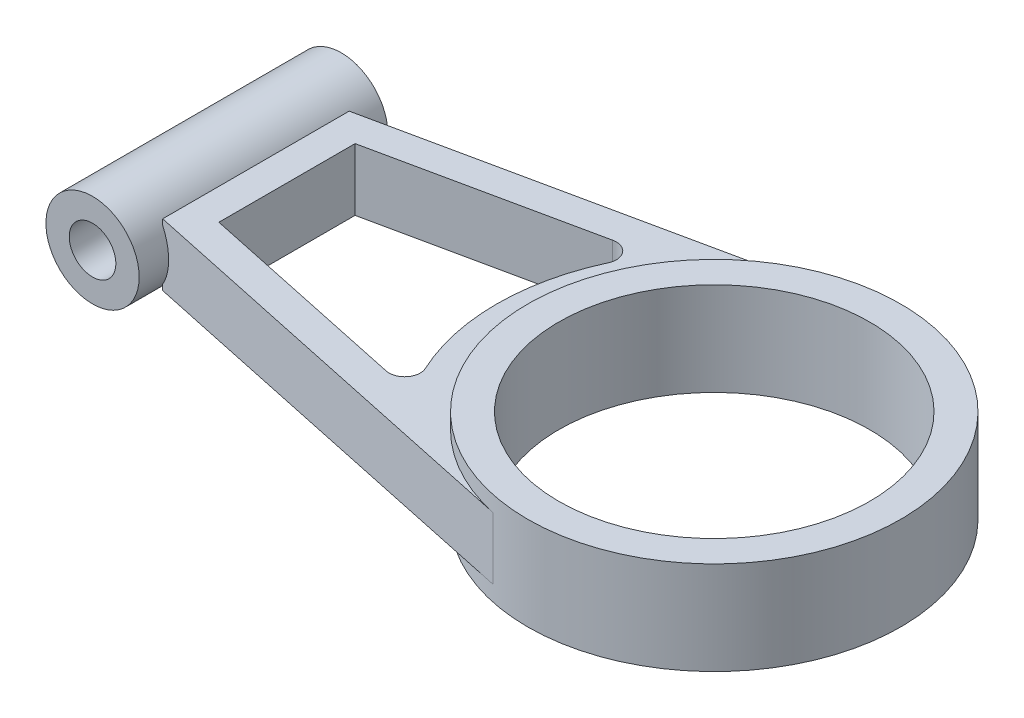
SolidWorks part; units mm, degrees
ref_plane "Alzado" through (0, 0, 0) normal (0, 0, 1) x (1, 0, 0)
ref_plane "Planta" through (0, 0, 0) normal (0, 1, 0) x (1, 0, 0)
ref_plane "Vista lateral" through (0, 0, 0) normal (1, 0, 0) x (0, 0, -1)
sketch "Croquis2" plane through (0, 0, 0) normal (0, 1, 0) x (1, 0, 0)
  line L0 (-147.4452, 30) -> (-12.4747, 58.6889)
  line L1 (-147.4452, 30) -> (-147.4452, -30)
  line L2 (-147.4452, -30) -> (-12.4747, -58.6889)
  line L3 (-137.4452, -21.9022) -> (-69.0844, -36.4327)
  line L4 (-137.4452, 21.9022) -> (-137.4452, -21.9022)
  line L5 (-137.4452, 21.9022) -> (-69.0844, 36.4327)
  line L6 (-147.4452, 30) -> (22.7929, 66.1852) construction
  line L7 (-147.4452, -30) -> (22.7929, -66.1852) construction
  line L9 (-137.4452, 21.9022) -> (24.872, 56.4037) construction
  line L10 (-137.4452, -21.9022) -> (24.872, -56.4037) construction
  arc A0 (-63.5086, 29.4391) -> (-63.5086, -29.4391) centre (0, 0) ccw
  arc A1 (-12.4747, -58.6889) -> (-12.4747, 58.6889) centre (0, 0) ccw
  arc A2 (-63.5086, 29.4391) -> (-69.0844, 36.4327) centre (-68.0449, 31.5419) ccw
  arc A3 (-69.0844, -36.4327) -> (-63.5086, -29.4391) centre (-68.0449, -31.5419) ccw
  circle A4 centre (0, 0) radius 50
  point P7 (-147.4452, 0)
  dimension "D1" = 140
  dimension "D2" = 120
  dimension "D7" = 10
  dimension "D8" = 10
  dimension "D9" = 100
  dimension "D3" = 0
  dimension "D4" = 24
  dimension "D5" = 10
  dimension "D6" = 60
extrude "Saliente-Extruir3" add sketch "Croquis2" along normal blind 30
sketch "Croquis4" plane through (0, 0, 0) normal (0, 1, 0) x (1, 0, 0)
  line L0 (-69.0844, 36.4327) -> (-137.4452, 21.9022) construction
  line L1 (-137.4452, -21.9022) -> (-69.0844, -36.4327) construction
  line L2 (-147.4452, -30) -> (-12.4747, -58.6889) construction
  line L3 (-137.4452, 21.9022) -> (-137.4452, -21.9022) construction
  line L4 (-147.4452, 30) -> (-147.4452, -30) construction
  line L5 (-12.4747, 58.6889) -> (-147.4452, 30) construction
  line L6 (-69.0844, 36.4327) -> (-137.4452, 21.9022)
  line L7 (-137.4452, -21.9022) -> (-69.0844, -36.4327)
  line L8 (-147.4452, -30) -> (-12.4747, -58.6889)
  line L9 (-137.4452, 21.9022) -> (-137.4452, -21.9022)
  line L10 (-147.4452, 30) -> (-147.4452, -30)
  line L11 (-12.4747, 58.6889) -> (-147.4452, 30)
  arc A0 (-63.5086, 29.4391) -> (-63.5086, -29.4391) centre (0, 0) ccw
  arc A1 (-12.4747, 58.6889) -> (-12.4747, -58.6889) centre (0, 0) ccw
  arc A2 (-63.5086, 29.4391) -> (-69.0844, 36.4327) centre (-68.0449, 31.5419) ccw construction
  arc A3 (-69.0844, -36.4327) -> (-63.5086, -29.4391) centre (-68.0449, -31.5419) ccw construction
  arc A4 (-63.5086, 29.4391) -> (-69.0844, 36.4327) centre (-68.0449, 31.5419) ccw
  arc A5 (-69.0844, -36.4327) -> (-63.5086, -29.4391) centre (-68.0449, -31.5419) ccw
extrude "Cortar-Extruir1" cut sketch "Croquis4" along normal blind 5
sketch "Croquis5" plane through (0, 30, 0) normal (0, 1, 0) x (1, 0, 0)
  line L0 (-147.4452, 30) -> (-147.4452, -30) construction
  line L1 (-147.4452, -30) -> (-12.4747, -58.6889) construction
  line L2 (-137.4452, -21.9022) -> (-69.0844, -36.4327) construction
  line L3 (-69.0844, 36.4327) -> (-137.4452, 21.9022) construction
  line L4 (-12.4747, 58.6889) -> (-147.4452, 30) construction
  line L5 (-147.4452, 30) -> (-147.4452, -30)
  line L6 (-147.4452, -30) -> (-12.4747, -58.6889)
  line L7 (-137.4452, -21.9022) -> (-69.0844, -36.4327)
  line L8 (-69.0844, 36.4327) -> (-137.4452, 21.9022)
  line L9 (-12.4747, 58.6889) -> (-147.4452, 30)
  line L10 (-137.4452, 21.9022) -> (-137.4452, -21.9022) construction
  line L11 (-137.4452, 21.9022) -> (-137.4452, -21.9022)
  arc A1 (-63.5086, 29.4391) -> (-63.5086, -29.4391) centre (0, 0) ccw
  arc A2 (-12.4747, 58.6889) -> (-12.4747, -58.6889) centre (0, 0) ccw
  arc A3 (-69.0844, -36.4327) -> (-63.5086, -29.4391) centre (-68.0449, -31.5419) ccw construction
  arc A4 (-63.5086, 29.4391) -> (-69.0844, 36.4327) centre (-68.0449, 31.5419) ccw construction
  arc A5 (-69.0844, -36.4327) -> (-63.5086, -29.4391) centre (-68.0449, -31.5419) ccw
  arc A6 (-63.5086, 29.4391) -> (-69.0844, 36.4327) centre (-68.0449, 31.5419) ccw
extrude "Cortar-Extruir2" cut sketch "Croquis5" against normal blind 5
sketch "Croquis7" plane through (0, 0, 0) normal (0, 0, 1) x (1, 0, 0)
  circle A0 centre (-160, 15) radius 15
  dimension "D1" = 30
  dimension "D2" = 160
extrude "Saliente-Extruir4" add sketch "Croquis7" along normal blind 40
extrude "Saliente-Extruir5" add sketch "Croquis7<2>" against normal blind 40
sketch "Croquis7<2>" plane through (0, 0, 0) normal (0, 0, 1) x (1, 0, 0) same geometry as "Croquis7"
sketch "Croquis8" plane through (0, 0, 40) normal (0, 0, 1) x (1, 0, 0)
  circle A0 centre (-160, 15) radius 7.5
  circle A1 centre (-160, 15) radius 15 construction
  dimension "D1" = 15
extrude "Cortar-Extruir3" cut sketch "Croquis8" against normal through all
